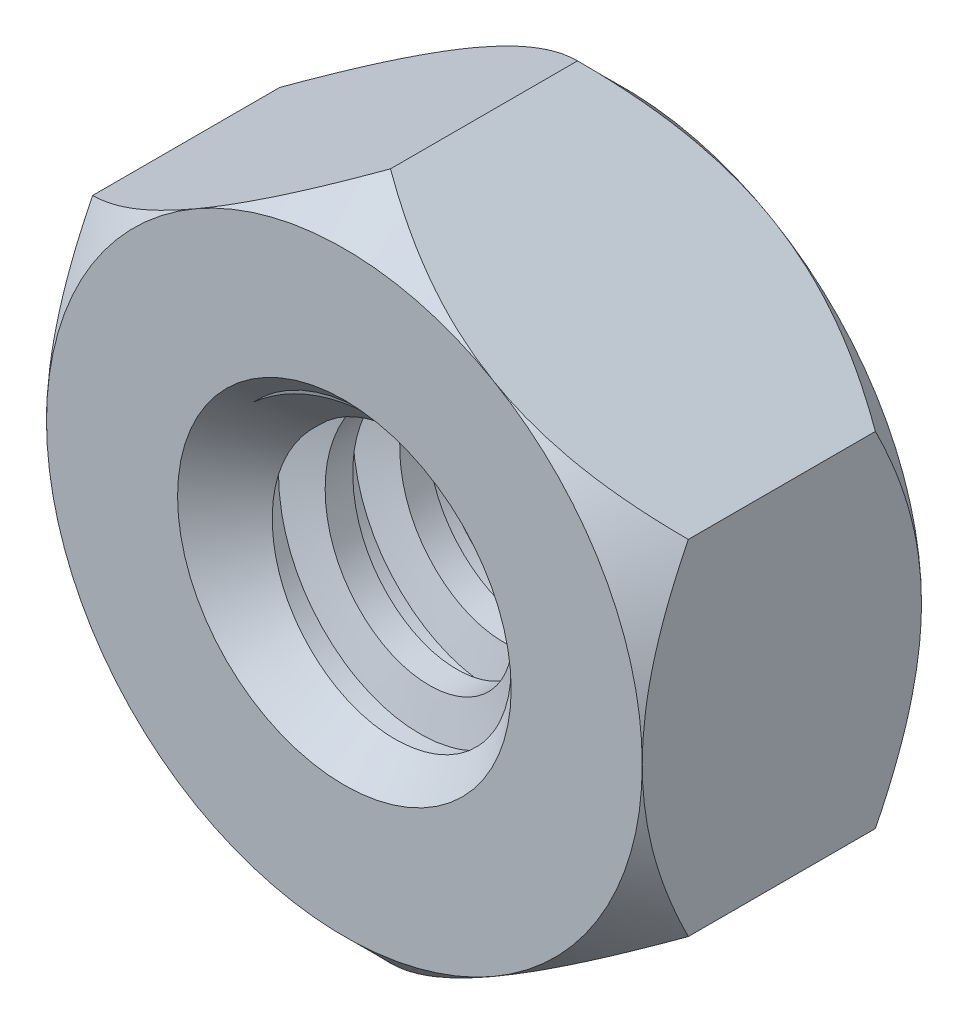
SolidWorks part; units mm, degrees
ref_plane "Front" through (0, 0, 0) normal (0, 0, 1) x (1, 0, 0)
ref_plane "Top" through (0, 0, 0) normal (0, 1, 0) x (1, 0, 0)
ref_plane "Right" through (0, 0, 0) normal (1, 0, 0) x (0, 0, -1)
sketch "Sketch1" plane through (0, 0, 0) normal (0, 0, 1) x (1, 0, 0)
  line L1 (0, -7.3323) -> (6.35, -3.6662)
  line L2 (6.35, -3.6662) -> (6.35, 3.6662)
  line L3 (6.35, 3.6662) -> (0, 7.3323)
  line L4 (0, 7.3323) -> (-6.35, 3.6662)
  line L5 (-6.35, 3.6662) -> (-6.35, -3.6662)
  line L6 (-6.35, -3.6662) -> (0, -7.3323)
  circle A0 centre (0, 0) radius 6.35 construction
  circle A1 centre (0, 0) radius 3.175
  dimension "Width" = 12.7
  dimension "ThreadDia" = 6.35
extrude "Boss-Extrude1" add sketch "Sketch1" along normal mid plane 5.9531
sketch "Sketch2" plane through (0, 0, 2.9766) normal (0, 0, 1) x (1, 0, 0)
  circle A0 centre (0, 0) radius 3.175 construction
  circle A1 centre (0, 0) radius 3.175
curve "Helix/Spiral1" pitch 1.5875 height 7.5406 radius 3.175 centre (0, 0, 2.9766) axis (0, 0, -1) start towards (0, 1, 0) parameters "Pitch"=1.5875
sketch "Sketch3" plane through (0, 0, 0) normal (1, 0, 0) x (0, 0, -1)
  line L0 (-2.9766, 3.175) -> (-3.1818, 2.3813)
  line L1 (-2.9766, 3.6662) -> (-2.9766, -3.6662) construction
  line L2 (-2.9766, 3.175) -> (-2.9766, -3.175) construction
  line L3 (-3.1818, 2.3813) -> (-3.7703, 2.3813)
  line L4 (-3.7703, 2.3813) -> (-3.9756, 3.175)
  line L5 (-3.9756, 3.175) -> (-2.9766, 3.175)
  line L6 (-3.8729, 2.7782) -> (-3.0792, 2.7782) construction
  line L7 (-3.4761, 2.7782) -> (-3.4761, 2.3813) construction
  spline S0 degree 3 poles (-2.9766, 3.175) (-2.9437, 3.175) (-2.8772, 3.0097) (-2.7782, 2.3035) (-2.6789, 1.2467) (-2.5797, 0) (-2.4805, -1.2467) (-2.3813, -2.3035) (-2.282, -3.0097) (-2.1828, -3.2577) (-2.0836, -3.0097) (-1.9844, -2.3035) (-1.8852, -1.2467) (-1.7859, 0) (-1.6867, 1.2467) (-1.5875, 2.3035) (-1.4883, 3.0097) (-1.3891, 3.2577) (-1.2898, 3.0097) (-1.1906, 2.3035) (-1.0914, 1.2467) (-0.9922, 0) (-0.893, -1.2467) (-0.7938, -2.3035) (-0.6945, -3.0097) (-0.5953, -3.2577) (-0.4961, -3.0097) (-0.3969, -2.3035) (-0.2977, -1.2467) (-0.1984, 0) (-0.0992, 1.2467) (0, 2.3035) (0.0992, 3.0097) (0.1984, 3.2577) (0.2977, 3.0097) (0.3969, 2.3035) (0.4961, 1.2467) (0.5953, 0) (0.6945, -1.2467) (0.7937, -2.3035) (0.893, -3.0097) (0.9922, -3.2577) (1.0914, -3.0097) (1.1906, -2.3035) (1.2898, -1.2467) (1.3891, 0) (1.4883, 1.2467) (1.5875, 2.3035) (1.6867, 3.0097) (1.7859, 3.2577) (1.8852, 3.0097) (1.9844, 2.3035) (2.0836, 1.2467) (2.1828, 0) (2.282, -1.2467) (2.3813, -2.3035) (2.4805, -3.0097) (2.5797, -3.2577) (2.6789, -3.0097) (2.7781, -2.3035) (2.8773, -1.2467) (2.9766, 0) (3.0758, 1.2467) (3.175, 2.3035) (3.2742, 3.0097) (3.3734, 3.2577) (3.4727, 3.0097) (3.5719, 2.3035) (3.6711, 1.2467) (3.7703, 0) (3.8695, -1.2467) (3.9688, -2.3035) (4.068, -3.0097) (4.1672, -3.2576) (4.2664, -3.0098) (4.3657, -2.3032) (4.4647, -1.2479) (4.5312, -0.413) (4.5641, 0) knots 0 0 0 0 0.013158 0.026316 0.039474 0.052632 0.065789 0.078947 0.092105 0.105263 0.118421 0.131579 0.144737 0.157895 0.171053 0.184211 0.197368 0.210526 0.223684 0.236842 0.25 0.263158 0.276316 0.289474 0.302632 0.315789 0.328947 0.342105 0.355263 0.368421 0.381579 0.394737 0.407895 0.421053 0.434211 0.447368 0.460526 0.473684 0.486842 0.5 0.513158 0.526316 0.539474 0.552632 0.565789 0.578947 0.592105 0.605263 0.618421 0.631579 0.644737 0.657895 0.671053 0.684211 0.697368 0.710526 0.723684 0.736842 0.75 0.763158 0.776316 0.789474 0.802632 0.815789 0.828947 0.842105 0.855263 0.868421 0.881579 0.894737 0.907895 0.921053 0.934211 0.947368 0.960526 0.973684 0.986842 1 1 1 1 construction
  dimension "D1" = 29
  dimension "D2" = 0.5885
  dimension "D3" = 0.7937
sketch "Sketch4" plane through (0, 0, 2.9766) normal (0, 0, 1) x (1, 0, 0)
  circle A0 centre (0, 0) radius 3.556
  circle A1 centre (0, 0) radius 3.175 construction
  dimension "D1" = 0.381
sketch "Sketch5" plane through (0, 0, -2.9766) normal (0, 0, -1) x (-1, 0, 0)
  circle A1 centre (0, 0) radius 3.556
  circle A2 centre (0, 0) radius 3.556
  dimension "D1" = 0
sweep "Sweep1" add profiles "Sketch3" path "Helix/Spiral1"
extrude "Cut-Extrude1" cut sketch "Sketch4" along normal through all
extrude "Cut-Extrude2" cut sketch "Sketch5" along normal through all
extrude "Cut-Extrude3" cut sketch "Sketch4<2>" against normal through all draft 45
sketch "Sketch4<2>" plane through (0, 0, 2.9766) normal (0, 0, 1) x (1, 0, 0) same geometry as "Sketch4"
extrude "Cut-Extrude4" cut sketch "Sketch5<2>" against normal through all draft 45
sketch "Sketch5<2>" plane through (0, 0, -2.9766) normal (0, 0, -1) x (-1, 0, 0) same geometry as "Sketch5"
sketch "Sketch6" plane through (0, 0, 2.9766) normal (0, 0, 1) x (1, 0, 0)
  line L0 (-6.35, 0) -> (0, 0) construction
  line L2 (-6.35, 3.6662) -> (-6.35, -3.6662) construction
  circle A0 centre (0, 0) radius 6.35
extrude "Cut-Extrude5" cut sketch "Sketch6" against normal through all draft 45 flip side to cut
sketch "Sketch7" plane through (0, 0, -2.9766) normal (0, 0, -1) x (-1, 0, 0)
  circle A1 centre (0, 0) radius 6.35
  circle A2 centre (0, 0) radius 6.35
  dimension "D1" = 0
extrude "Cut-Extrude6" cut sketch "Sketch7" against normal through all draft 45 flip side to cut
equation "\"D3@Helix/Spiral1\" = \"Height@Boss-Extrude1\"+\"Pitch@Helix/Spiral1\""
equation "\"D2@Sketch3\" = \"Pitch@Helix/Spiral1\"*.3707"
equation "\"D3@Sketch3\" = \"Pitch@Helix/Spiral1\"*.5"
